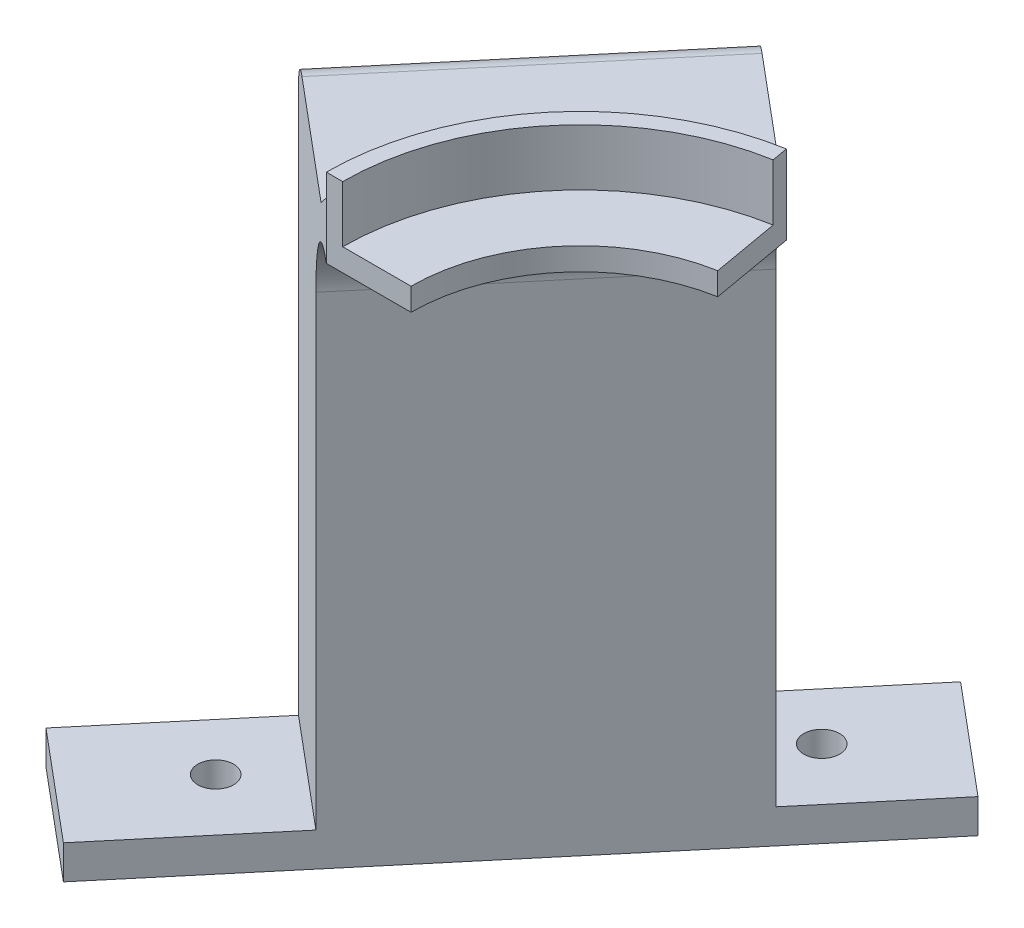
SolidWorks part; units mm, degrees
ref_plane "Front Plane" through (0, 0, 0) normal (0, 0, 1) x (1, 0, 0)
ref_plane "Top Plane" through (0, 0, 0) normal (0, 1, 0) x (1, 0, 0)
ref_plane "Right Plane" through (0, 0, 0) normal (1, 0, 0) x (0, 0, -1)
sketch "Sketch1" plane through (0, 0, 0) normal (0, 1, 0) x (1, 0, 0)
  line L0 (0, 0) -> (-45, 0)
  line L1 (0, 0) -> (-7.8142, 44.3163)
  circle A0 centre (0, 0) radius 42.1
  circle A1 centre (0, 0) radius 45
  circle A2 centre (0, 0) radius 30
  point P5 (-26.607, 36.2914)
  dimension "D1" = 84.2
  dimension "D2" = 90
  dimension "D3" = 60
  dimension "D4" = 80
extrude "Boss-Extrude1" add sketch "Sketch1" along normal blind 4 contours A2 L1 A0 L0 | L1 A1 L0 A0 region at (-25.6654, 0, -21.5358) region at (-43.55, 0, -0.5818)
extrude "Boss-Extrude2" add sketch "Sketch1<3>" along normal blind 14 contours L1 A1 L0 A0 region at (-43.55, 0, -0.5818)
sketch "Sketch1<3>" plane through (0, 0, 0) normal (0, 1, 0) x (1, 0, 0) same geometry as "Sketch1"
ref_plane "Plane1" through (0, -2.54, 0) normal (0, -1, 0) x (-1, 0, 0)
ref_plane "Plane2" through (0, -106.04, 0) normal (0, -1, 0) x (-1, 0, 0)
sketch "Sketch2" plane through (0, -106.04, 0) normal (0, -1, 0) x (-1, 0, 0)
  line L2 (7.8142, 44.3163) -> (5.2094, 29.5442)
  line L3 (30, 0) -> (45, 0)
  line L4 (7.8142, 44.3163) -> (5.2094, 29.5442)
  line L5 (30, 0) -> (45, 0)
  arc A2 (45, 0) -> (7.8142, 44.3163) centre (0, 0) ccw
  arc A3 (30, 0) -> (5.2094, 29.5442) centre (0, 0) ccw
  arc A4 (45, 0) -> (7.8142, 44.3163) centre (0, 0) ccw
  arc A5 (30, 0) -> (5.2094, 29.5442) centre (0, 0) ccw
  dimension "D1" = 0
sketch "Sketch3" plane through (0, 0, 0) normal (0, -1, 0) x (1, 0, 0)
  line L0 (-7.8142, -44.3163) -> (-45, 0)
  line L1 (-45, 0) -> (-75.6418, -25.7115)
  line L2 (-75.6418, -25.7115) -> (-38.4559, -70.0279)
  line L3 (-38.4559, -70.0279) -> (-7.8142, -44.3163)
  dimension "D1" = 40
extrude "Boss-Extrude3" add sketch "Sketch3" against normal up to surface (4 mm away) contours L3 L0 L1 L2 up to face at (-24.3855, 4, -20.4618)
sketch "Sketch4" plane through (0, 0, 0) normal (0, -1, 0) x (1, 0, 0)
  line L0 (-38.4559, -70.0279) -> (-19.3048, -53.9582)
  line L1 (-38.4559, -70.0279) -> (-7.8142, -44.3163) construction
  line L2 (-19.3048, -53.9582) -> (-56.4907, -9.6418)
  line L3 (-45, 0) -> (-75.6418, -25.7115) construction
  line L4 (-56.4907, -9.6418) -> (-75.6418, -25.7115)
  line L5 (-75.6418, -25.7115) -> (-38.4559, -70.0279)
  dimension "D1" = 25
extrude "Boss-Extrude4" add sketch "Sketch4" along normal blind 103.5
fillet "Fillet1" radius 15 1 edges at (-37.8978, 0, -31.8)
fillet "Fillet2" radius 5 1 edges at (-57.0489, 4, -47.8697)
chamfer "Chamfer1" distance 6 angle 45 1 edges at (-34.472, 4, -28.9254)
sketch "Sketch6" plane through (18.5929, 0, -22.1582) normal (0.6428, 0, -0.766) x (-0.766, 0, -0.6428)
  line L0 (74.472, -1) -> (74.472, -103.5) construction
  line L1 (49.472, -103.5) -> (74.472, -103.5)
  line L2 (49.472, -103.5) -> (49.472, -97.5)
  line L3 (49.472, -97.5) -> (74.472, -97.5)
  line L4 (74.472, -103.5) -> (74.472, -97.5)
  dimension "D1" = 6
extrude "Boss-Extrude5" add sketch "Sketch6" along normal blind 25.4
sketch "Sketch7" plane through (-18.5929, 0, 22.1582) normal (-0.6428, 0, 0.766) x (0.766, 0, 0.6428)
  line L4 (-49.472, -103.5) -> (-49.472, -97.5)
  line L5 (-74.472, -103.5) -> (-49.472, -103.5)
  line L6 (-74.472, -97.5) -> (-74.472, -103.5)
  line L7 (-49.472, -97.5) -> (-74.472, -97.5)
  line L8 (-49.472, -103.5) -> (-49.472, -97.5)
  line L9 (-74.472, -103.5) -> (-49.472, -103.5)
  line L10 (-74.472, -97.5) -> (-74.472, -103.5)
  line L11 (-49.472, -97.5) -> (-74.472, -97.5)
  dimension "D1" = 0
extrude "Boss-Extrude6" add sketch "Sketch7" along normal blind 31.75
sketch "Sketch8" plane through (0, -97.5, 0) normal (0, 1, 0) x (1, 0, 0)
  circle A1 centre (-24.9091, 67.6646) radius 2.5527
  circle A2 centre (-24.9091, 67.6646) radius 2.5527
  circle A3 centre (-73.8895, 9.292) radius 2.5527
  circle A4 centre (-73.8895, 9.292) radius 2.5527
  dimension "D1" = 0
  dimension "D2" = 0
extrude "Cut-Extrude1" cut sketch "Sketch8" against normal blind 25.4 contours A4 | A2 region at (-73.8895, -97.5, -9.292)
sketch "Sketch9" plane through (0, -103.5, 0) normal (0, -1, 0) x (1, 0, 0)
  circle A0 centre (-73.8895, -9.292) radius 3.175
  circle A1 centre (-24.9091, -67.6646) radius 3.175
  dimension "D1" = 6.35
  dimension "D2" = 6.35
extrude "Cut-Extrude2" cut sketch "Sketch9" against normal blind 25.4
sketch "Sketch10" plane through (0, -97.5, 0) normal (0, 1, 0) x (1, 0, 0)
  line L1 (-76.8992, -14.6801) -> (-22.1291, -14.6801)
  line L2 (-76.8992, -14.6801) -> (-76.8992, 89.4854)
  line L3 (-76.8992, 89.4854) -> (-22.1291, 89.4854)
  line L4 (-22.1291, -14.6801) -> (-22.1291, 89.4854)
  line L5 (-144.4229, -81.7018) -> (69.164, -81.7018)
  line L6 (-144.4229, -81.7018) -> (-144.4229, 136.0266)
  line L7 (-144.4229, 136.0266) -> (69.164, 136.0266)
  line L8 (69.164, -81.7018) -> (69.164, 136.0266)
  line M11 (-75.6418, 25.7115) -> (-96.0503, 1.3896)
  line M12 (-96.0503, 1.3896) -> (-76.8992, -14.6801)
extrude "Cut-Extrude3" [suppressed] cut sketch "Sketch10" along normal blind 132.4 contours L5 L8 L7 L6 L4 L1 L2 L3 M12 M11 | L2 L1 L4 L3
